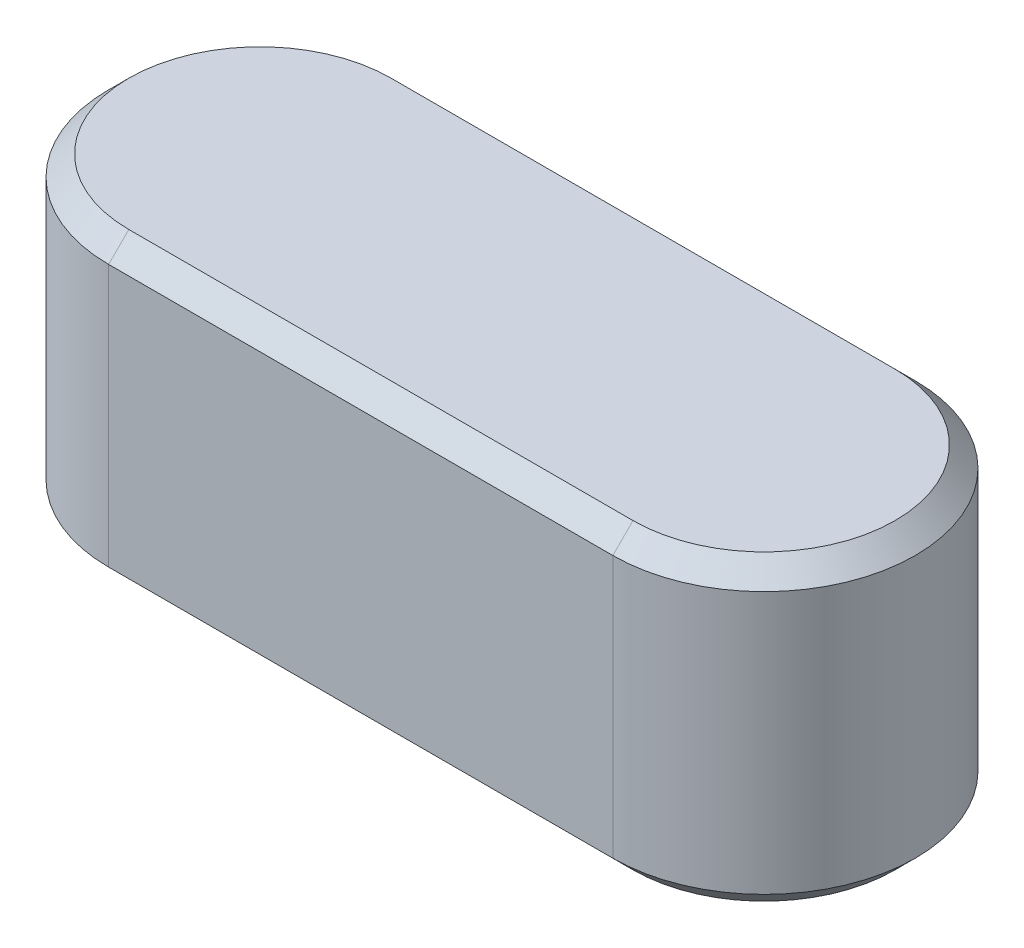
SolidWorks part; units mm, degrees
material "S45C"
ref_plane "Front Plane" through (0, 0, 0) normal (0, 0, 1) x (1, 0, 0)
ref_plane "Top Plane" through (0, 0, 0) normal (0, 1, 0) x (1, 0, 0)
ref_plane "Right Plane" through (0, 0, 0) normal (1, 0, 0) x (0, 0, -1)
sketch "Sketch1" plane through (0, 0, 0) normal (0, 1, 0) x (1, 0, 0)
  line L0 (-4, 0) -> (4, 0) construction
  line L1 (0, 1.5) -> (0, -1.5) construction
  line L3 (-4, 1.5) -> (4, 1.5)
  line L4 (-4, 1.5) -> (-4, -1.5)
  line L5 (-4, -1.5) -> (4, -1.5)
  line L6 (4, 1.5) -> (4, -1.5)
  dimension "L" = 8
  dimension "B" = 3
extrude "Boss-Extrude1" add sketch "Sketch1" along normal blind 3
chamfer "Chamfer1" [suppressed] distance 0.2 angle 45
fillet "Fillet1" 2 edges at (-4, 1.5, 1.5) (-4, 1.5, -1.5) type full round first side face at (0, 1.5, 1.5) second side face at (0, 1.5, -1.5) middle face at (-4, 1.5, 0)
fillet "Fillet2" 2 edges at (4, 1.5, 1.5) (4, 1.5, -1.5) type full round first side face at (0.75, 1.5, 1.5) second side face at (0.75, 1.5, -1.5) middle face at (4, 1.5, 0)
chamfer "Chamfer2" distance 0.2 angle 45 8 edges at (0, 0, -1.5) (-4, 0, 0) (4, 0, 0) (0, 0, 1.5) (0, 3, -1.5) (-4, 3, 0) (4, 3, 0) (0, 3, 1.5)
